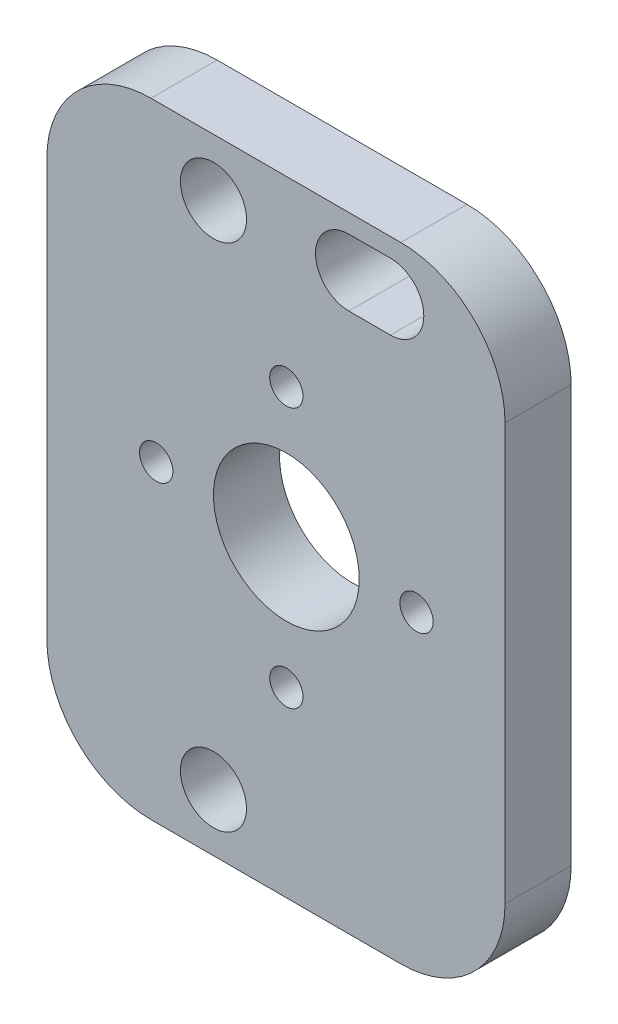
SolidWorks part; units mm, degrees
material "6061-T6 (SS)"
ref_plane "Front Plane" through (0, 0, 0) normal (0, 0, 1) x (1, 0, 0)
ref_plane "Top Plane" through (0, 0, 0) normal (0, 1, 0) x (1, 0, 0)
ref_plane "Right Plane" through (0, 0, 0) normal (1, 0, 0) x (0, 0, -1)
sketch "Sketch2" plane through (0, 0, 0) normal (0, 0, 1) x (1, 0, 0)
  line L0 (0, 0) -> (21, 0) construction
  line L1 (-23, -30) -> (21, -30)
  line L2 (-23, -30) -> (-23, 30)
  line L3 (-23, 30) -> (21, 30)
  line L4 (21, -30) -> (21, 30)
  line L5 (-23, -30) -> (21, 30) construction
  line L6 (-23, 30) -> (21, -30) construction
  circle A0 centre (0, 0) radius 7
  circle A1 centre (-7, 24.5) radius 3.175
  circle A2 centre (-7, -24.5) radius 3.175
  point P3 (-1, 0)
  point P8 (0, 12.5)
  point P12 (12.5, 0)
  point P13 (0, -12.5)
  point P14 (-12.5, 0)
  point P15 (0, 0)
  dimension "D1" = 14
  dimension "D9" = 6.35
  dimension "D2" = 30
  dimension "D3" = 23
  dimension "D4" = 21
  dimension "D5" = 12.5
  dimension "D7" = 5.5
  dimension "D8" = 16
  dimension "D6" = 4
extrude "Boss-Extrude1" add sketch "Sketch2" along normal mid plane 6.35
hole_wizard "M3 Clearance Hole1" positions "Sketch3" profile "Sketch4" hole size "M3" standard "ANSI Metric" end condition through all
sketch "Sketch3" plane through (0, 0, 3.175) normal (0, 0, 1) x (1, 0, 0)
  point P0 (0, 12.5)
  point P3 (12.5, 0)
  point P6 (0, -12.5)
  point P9 (-12.5, 0)
sketch "Sketch4" plane through (0, 12.5, 3.175) normal (1, 0, 0) x (0, -1, 0)
  line L0 (0, 0) -> (0, 6.35)
  line L1 (0, 6.35) -> (1.6, 6.35)
  line L2 (1.6, 6.35) -> (1.6, 0)
  line L5 (1.6, 0) -> (0, 0)
  line L11 (0, -6.35) -> (0, 107.95) construction
  dimension "Thru Hole Dia." = 3.2
  dimension "Thru Hole Depth" = 6.35
fillet "Fillet1" radius 10 4 edges at (21, -30, 0) (21, 30, 0) (-23, -30, 0) (-23, 30, 0)
sketch "Sketch5" plane through (0, 0, 3.175) normal (0, 0, 1) x (1, 0, 0)
  line L1 (6, 25) -> (10, 25) construction
  line L2 (6, 28.2) -> (10, 28.2)
  line L3 (6, 21.8) -> (10, 21.8)
  line L4 (11, 30) -> (-13, 30) construction
  line L5 (21, -20) -> (21, 20) construction
  arc A1 (6, 28.2) -> (6, 21.8) centre (6, 25) ccw
  arc A2 (10, 21.8) -> (10, 28.2) centre (10, 25) ccw
  point P2 (8, 25)
  dimension "D2" = 3.2
  dimension "D1" = 5
  dimension "D3" = 15
  dimension "D4" = 4
extrude "Cut-Extrude1" cut sketch "Sketch5" against normal through all
equation "\"D9@Sketch2\"=0.25in"
